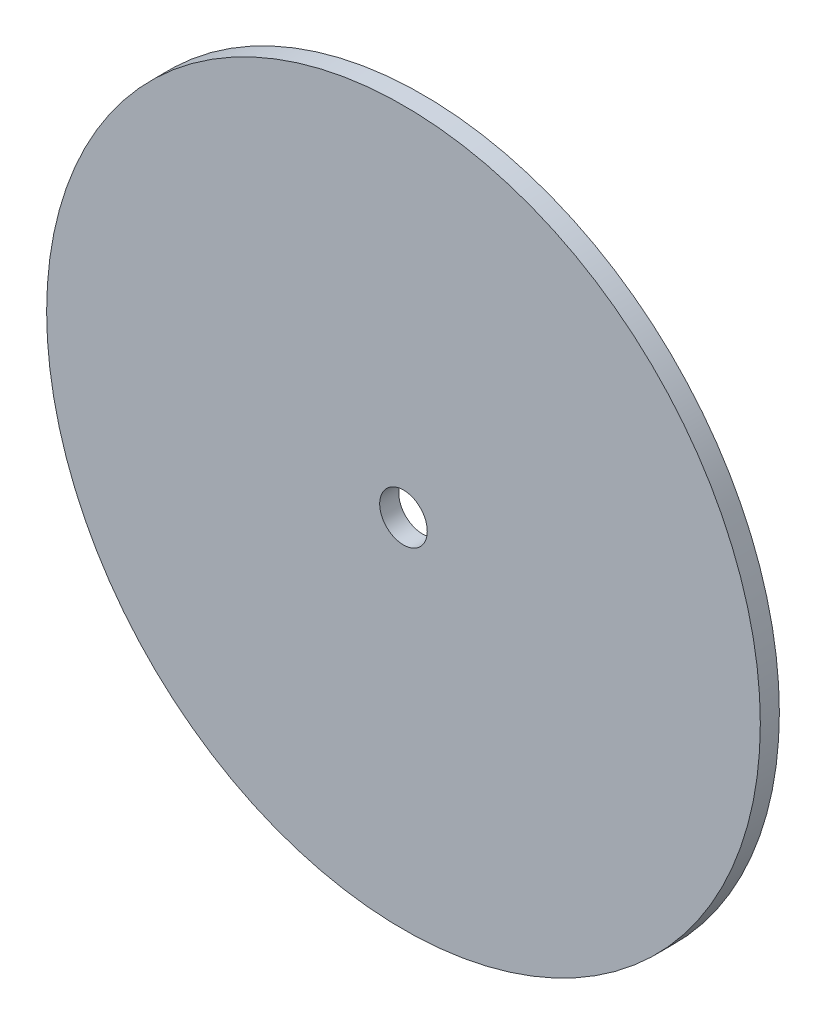
SolidWorks part; units mm, degrees
ref_plane "Front Plane" through (0, 0, 0) normal (0, 0, 1) x (1, 0, 0)
ref_plane "Top Plane" through (0, 0, 0) normal (0, 1, 0) x (1, 0, 0)
ref_plane "Right Plane" through (0, 0, 0) normal (1, 0, 0) x (0, 0, -1)
sketch "Sketch1" plane through (0, 0, 0) normal (0, 0, 1) x (1, 0, 0)
  circle A0 centre (0, 0) radius 37.5
  dimension "D1" = 75
base flange "Base-Flange1" sketch "Sketch1" thickness 2 reverse thickness direction no parameters "D1"=0.7366
sketch "Sketch6" plane through (0, 0, 0) normal (0, 0, 1) x (1, 0, 0)
  circle A1 centre (0, 0) radius 2.5
  dimension "D1" = 5
extrude "Cut-Extrude1" cut sketch "Sketch6" against normal blind 10 normal cut yes
sketch "Bend-Lines1" plane through (0, 0, 0) normal (0, 1, 0) x (1, 0, 0)
sketch "Bounding-Box1" plane through (0, 0, 0) normal (0, 1, 0) x (1, 0, 0)
sheet metal parameters "Sheet-Metal1" thickness 2 parameters "D1"=0.7366
flat pattern "Flat-Pattern1" [suppressed]
sketch "Bend-Lines2" plane through (0, 0, 0) normal (0, 1, 0) x (1, 0, 0)
sketch "Bounding-Box2" [suppressed] plane through (0, 0, 0) normal (0, 1, 0) x (1, 0, 0)
sheet metal parameters "Sheet-Metal2" thickness 2 parameters "D1"=0.7366
flat pattern "Flat-Pattern1"
sketch "Bend-Lines2" plane through (0, 0, 0) normal (0, 1, 0) x (1, 0, 0)
sketch "Bounding-Box2" [suppressed] plane through (0, 0, 0) normal (0, 1, 0) x (1, 0, 0)
